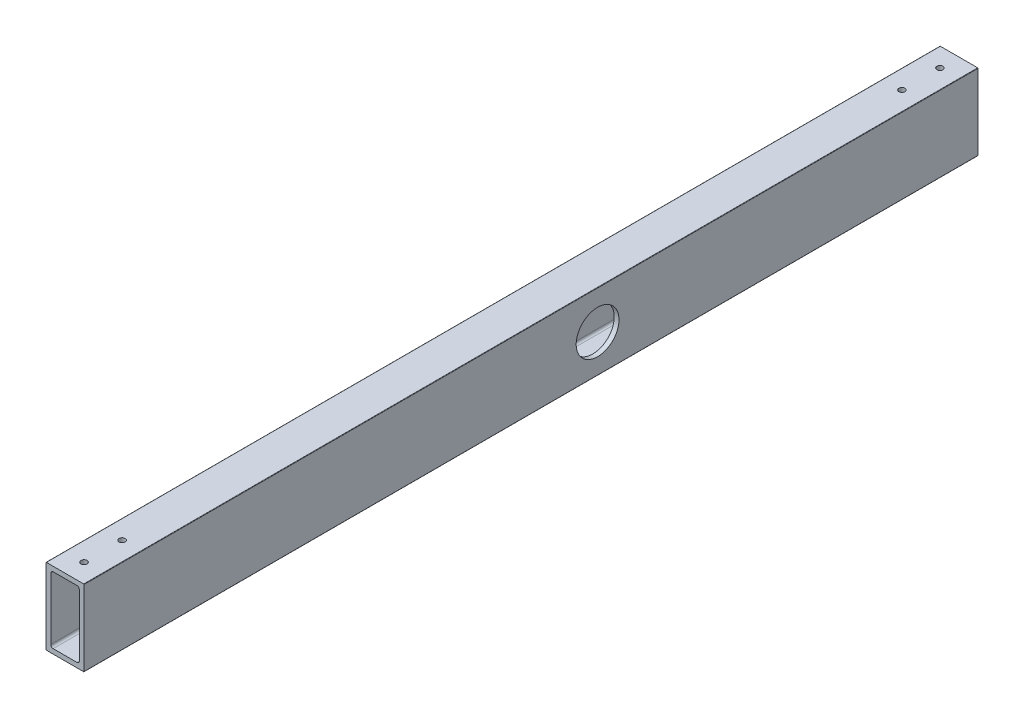
SolidWorks part; units mm, degrees
material "3.0205 (EN-AW 1200)"
ref_plane "Front Plane" through (0, 0, 0) normal (0, 0, 1) x (1, 0, 0)
ref_plane "Top Plane" through (0, 0, 0) normal (0, 1, 0) x (1, 0, 0)
ref_plane "Right Plane" through (0, 0, 0) normal (1, 0, 0) x (0, 0, -1)
ref_plane "Plane1" through (0, 0, 0) normal (0, 0, -1) x (-1, 0, 0)
sketch "Sketch1" plane through (0, 0, 0) normal (0, 0, -1) x (-1, 0, 0)
  line L0 (-3.175, 46.0375) -> (-3.175, 4.7625)
  line L1 (-4.7625, 3.175) -> (-20.6375, 3.175)
  line L2 (-22.225, 4.7625) -> (-22.225, 46.0375)
  line L3 (-20.6375, 47.625) -> (-4.7625, 47.625)
  line L4 (0, 0.254) -> (0, 50.546)
  line L5 (-0.254, 50.8) -> (-25.146, 50.8)
  line L6 (-25.4, 50.546) -> (-25.4, 0.254)
  line L7 (-25.146, 0) -> (-0.254, 0)
  arc A0 (-3.175, 4.7625) -> (-4.7625, 3.175) centre (-4.7625, 4.7625) cw
  arc A1 (-20.6375, 3.175) -> (-22.225, 4.7625) centre (-20.6375, 4.7625) cw
  arc A2 (-22.225, 46.0375) -> (-20.6375, 47.625) centre (-20.6375, 46.0375) cw
  arc A3 (-4.7625, 47.625) -> (-3.175, 46.0375) centre (-4.7625, 46.0375) cw
  arc A4 (-0.254, 0) -> (0, 0.254) centre (-0.254, 0.254) ccw
  arc A5 (0, 50.546) -> (-0.254, 50.8) centre (-0.254, 50.546) ccw
  arc A6 (-25.146, 50.8) -> (-25.4, 50.546) centre (-25.146, 50.546) ccw
  arc A7 (-25.4, 0.254) -> (-25.146, 0) centre (-25.146, 0.254) ccw
extrude "Boss-Extrude1" add sketch "Sketch1" against normal blind 596.9
sketch "Sketch2" plane through (0, 50.8, 0) normal (0, 1, 0) x (1, 0, 0)
  line L0 (0.254, -596.9) -> (25.146, -596.9) construction
  line L1 (25.146, -298.45) -> (0, -298.45) construction
  line L2 (25.146, -596.9) -> (25.146, 0) construction
  line L3 (0, -596.9) -> (0, 0) construction
  circle A0 centre (12.7, -584.2) radius 2.032
  circle A1 centre (12.7, -558.8) radius 2.032
  circle A2 centre (12.7, -38.1) radius 2.032
  circle A3 centre (12.7, -12.7) radius 2.032
  dimension "D1" = 4.064
  dimension "D2" = 4.064
  dimension "D3" = 12.7
  dimension "D4" = 25.4
extrude "Cut-Extrude1" cut sketch "Sketch2" against normal through all
ref_plane "Plane2" through (224.155, 46.0375, 596.9) normal (0, 0, -1) x (-1, 0, 0)
sketch "Sketch5" plane through (25.4, 0, 0) normal (1, 0, 0) x (0, 0, -1)
  line L0 (-596.9, 50.546) -> (0, 50.546) construction
  line L2 (0, 50.546) -> (0, 0.254) construction
  circle A0 centre (-254, 25.146) radius 14.2875
  dimension "D1" = 28.575
  dimension "D2" = 25.4
  dimension "D3" = 254
extrude "Cut-Extrude2" cut sketch "Sketch5" against normal through all
